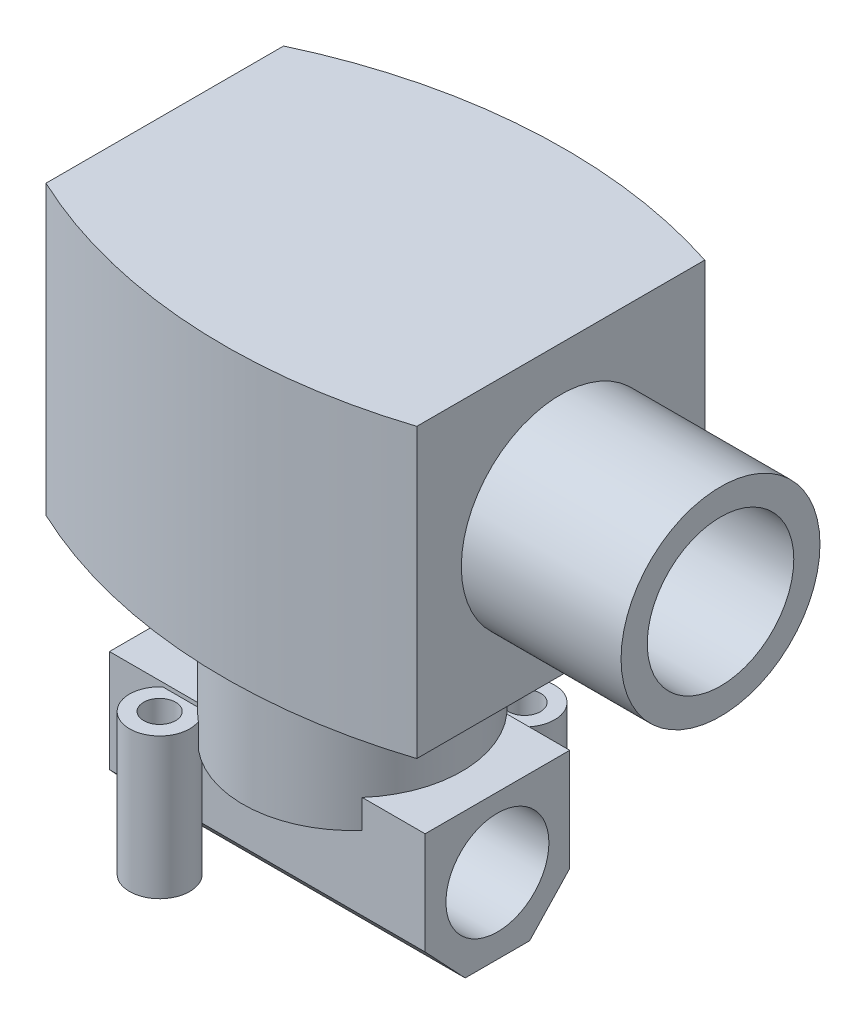
SolidWorks part; units mm, degrees
material "AISI 304"
ref_plane "Front" through (0, 0, 0) normal (0, 0, 1) x (1, 0, 0)
ref_plane "Top" through (0, 0, 0) normal (0, 1, 0) x (1, 0, 0)
ref_plane "Right" through (0, 0, 0) normal (1, 0, 0) x (0, 0, -1)
ref_axis "Axis1" through (0, 0, 55) along (0, 0, -1)
sketch "Sketch1" plane through (0, 0, 0) normal (0, 1, 0) x (1, 0, 0)
  line L0 (-25, 0) -> (25, 0) construction
  line L1 (-25, 15) -> (-25, -15)
  line L2 (25, 18.18) -> (25, -18.18)
  line L3 (4.0124, 21.5) -> (4.0124, -21.5) construction
  arc A0 (-25, 15) -> (25, 18.18) centre (4.0124, -46.4975) cw
  arc A1 (-25, -15) -> (25, -18.18) centre (4.0124, 46.4975) ccw
  point P4 (0, 0)
  point P8 (-25, 0)
  point P11 (25, 0)
  dimension "D1" = 36.36
  dimension "D2" = 30
  dimension "D3" = 50
  dimension "D4" = 43
extrude "Boss-Extrude1" add sketch "Sketch1" against normal blind 36.33
sketch "Sketch2" plane through (25, 0, 0) normal (1, 0, 0) x (0, 0, -1)
  line L0 (0, 0) -> (0, -36.33) construction
  line L1 (-18.18, 0) -> (18.18, 0) construction
  line L2 (-18.18, -36.33) -> (18.18, -36.33) construction
  circle A0 centre (0, -18.165) radius 12.56
  circle A1 centre (0, -18.165) radius 9.25
  dimension "D1" = 25.12
  dimension "D2" = 18.5
extrude "Boss-Extrude2" add sketch "Sketch2" along normal blind 20.17
sketch "Sketch3" plane through (0, -36.33, 0) normal (0, -1, 0) x (1, 0, 0)
  line L0 (-25, 0) -> (25, 0) construction
  line L1 (-25, -15) -> (-25, 15) construction
  line L2 (25, 18.18) -> (25, -18.18) construction
  line L3 (-15.13, 18.75) -> (-15.13, -18.75) construction
  circle A0 centre (-1.315, 0) radius 13.815
  arc A1 (25, 18.18) -> (-25, 15) centre (4.0124, -46.4975) ccw construction
  arc A2 (-25, -15) -> (25, -18.18) centre (4.0124, 46.4975) ccw construction
  dimension "D1" = 27.63
  dimension "D2" = 9.87
extrude "Boss-Extrude3" add sketch "Sketch3" along normal blind 20.35
sketch "Sketch4" plane through (25, 0, 0) normal (1, 0, 0) x (0, 0, -1)
  line L0 (0, 0) -> (0, -56.68) construction
  line L1 (-18.18, 0) -> (18.18, 0) construction
  line L2 (-13.815, -56.68) -> (13.815, -56.68) construction
  line L3 (-9.13, -66) -> (-9.13, -53.08)
  line L4 (-9.13, -53.08) -> (9.13, -53.08)
  line L5 (9.13, -53.08) -> (9.13, -66)
  line L6 (-4.07, -71.38) -> (4.07, -71.38)
  line L7 (-9.13, -66) -> (-4.07, -71.38)
  line L8 (4.07, -71.38) -> (9.13, -66)
  line L9 (-13.815, -36.33) -> (13.815, -36.33) construction
  point P10 (0, -53.08)
  point P13 (0, -71.38)
  point P14 (-4.07, -59.4353)
  dimension "D1" = 12.92
  dimension "D2" = 18.26
  dimension "D3" = 8.14
  dimension "D4" = 18.3
  dimension "D5" = 16.75
extrude "Boss-Extrude4" add sketch "Sketch4" against normal blind 47.86
sketch "Sketch5" plane through (25, 0, 0) normal (1, 0, 0) x (0, 0, -1)
  line L6 (-9.13, -66) -> (-4.07, -71.38)
  line L7 (-4.07, -71.38) -> (4.07, -71.38)
  line L8 (4.07, -71.38) -> (9.13, -66)
  line L9 (9.13, -66) -> (9.13, -53.08)
  line L10 (9.13, -53.08) -> (-9.13, -53.08)
  line L11 (-9.13, -53.08) -> (-9.13, -66)
  line L12 (-9.13, -66) -> (-4.07, -71.38)
  line L13 (-4.07, -71.38) -> (4.07, -71.38)
  line L14 (4.07, -71.38) -> (9.13, -66)
  line L15 (9.13, -66) -> (9.13, -53.08)
  line L16 (9.13, -53.08) -> (-9.13, -53.08)
  line L17 (-9.13, -53.08) -> (-9.13, -66)
  dimension "D1" = 0
extrude "Cut-Extrude1" cut sketch "Sketch5" against normal blind 8
sketch "Sketch6" plane through (17, 0, 0) normal (1, 0, 0) x (0, 0, -1)
  line L0 (0, -53.08) -> (0, -71.38) construction
  line L1 (9.13, -53.08) -> (-9.13, -53.08) construction
  line L2 (-4.07, -71.38) -> (4.07, -71.38) construction
  circle A0 centre (0, -61.8817) radius 6.5
  point P8 (0, -61.325)
  point P9 (0, -61.8817)
  dimension "D1" = 13
  dimension "D2" = 9.4983
extrude "Cut-Extrude2" cut sketch "Sketch6" against normal through all
sketch "Sketch7" plane through (0, -71.38, 0) normal (0, -1, 0) x (1, 0, 0)
  line L0 (-22.86, 0) -> (17, 0) construction
  line L1 (-22.86, 4.07) -> (-22.86, -4.07) construction
  line L2 (17, 4.07) -> (17, -4.07) construction
  line L3 (-13.64, 9.13) -> (-13.64, -9.13) construction
  line L4 (-22.86, 9.13) -> (17, 9.13) construction
  line L5 (-22.86, -9.13) -> (17, -9.13) construction
  line L6 (8.41, 9.13) -> (8.41, -9.13) construction
  line L7 (-13.64, 9.13) -> (-13.64, 12.01) construction
  line L8 (8.41, -9.13) -> (8.41, -12.01) construction
  line L9 (-9.84, 9.13) -> (-9.84, 15.81) construction
  line L10 (-22.86, 9.13) -> (-22.86, 4.07) construction
  line L11 (12.21, -9.13) -> (12.21, -15.81) construction
  line L12 (-17.44, 9.13) -> (-17.44, 15.81) construction
  line L13 (-17.44, 15.81) -> (-9.84, 15.81) construction
  line L14 (12.21, -15.81) -> (4.61, -15.81) construction
  line L15 (4.61, -15.81) -> (4.61, -9.13) construction
  line L16 (-11.6831, -9.13) -> (9.0531, -9.13) construction
  circle A0 centre (-13.64, 12.01) radius 3.8
  circle A1 centre (8.41, -12.01) radius 3.8
  point P30 (12.21, -9.13)
  dimension "D1" = 7.6
  dimension "D2" = 12.01
  dimension "D3" = 13.02
  dimension "D4" = 29.65
extrude "Boss-Extrude5" add sketch "Sketch7" against normal blind 17.8
hole_wizard "#10-32 Tapped Hole1" positions "Sketch9" profile "Sketch10" tap size "#10-32" standard "ANSI Inch" end condition up to next
sketch "Sketch9" plane through (0, -71.38, 0) normal (0, -1, 0) x (-1, 0, 0)
  point P0 (13.64, -12.01)
  point P3 (-8.41, 12.01)
sketch "Sketch10" plane through (-13.64, -71.38, 12.01) normal (1, 0, 0) x (0, 0, -1)
  line L0 (0, 0) -> (0, 17.8)
  line L1 (0, 17.8) -> (2.0193, 17.8)
  line L2 (2.0193, 17.8) -> (2.0193, 0)
  line L5 (2.0193, 0) -> (0, 0)
  line L11 (0, -6.35) -> (0, 107.95) construction
  dimension "Thru Tap Drill Dia." = 4.0386
  dimension "Thru Tap Drill Depth" = 17.8
cosmetic thread "Hole Thread1" parameters "D2"=4.826
cosmetic thread "Hole Thread2" parameters "D2"=4.826
